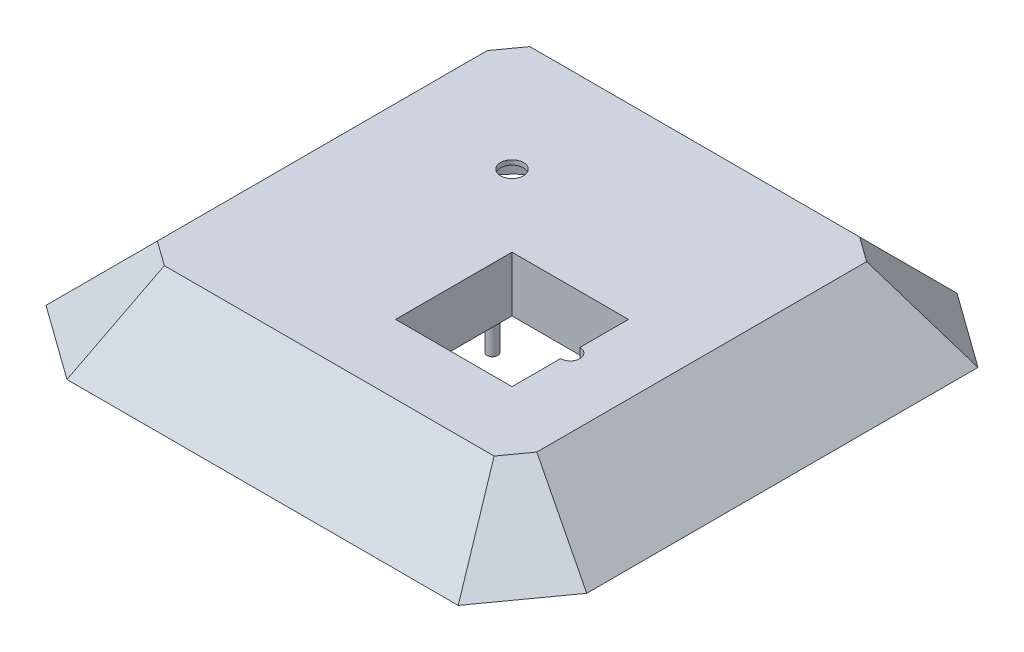
SolidWorks part; units mm, degrees
ref_plane "Front Plane" through (0, 0, 0) normal (0, 0, 1) x (1, 0, 0)
ref_plane "Top Plane" through (0, 0, 0) normal (0, 1, 0) x (1, 0, 0)
ref_plane "Right Plane" through (0, 0, 0) normal (1, 0, 0) x (0, 0, -1)
sketch "Sketch1" plane through (0, 0, 0) normal (0, 1, 0) x (1, 0, 0)
  line L0 (-47.3454, -21.7516) -> (37.6546, -21.7516)
  line L1 (37.6546, -21.7516) -> (49.3368, -5.5181)
  line L2 (49.3368, -5.5181) -> (49.3368, 79.4819)
  line L3 (49.3368, 79.4819) -> (33.1033, 91.1641)
  line L4 (33.1033, 91.1641) -> (-51.8967, 91.1641)
  line L5 (-51.8967, 91.1641) -> (-63.5789, 74.9306)
  line L6 (-63.5789, 74.9306) -> (-63.5789, -10.0694)
  line L7 (-63.5789, -10.0694) -> (-47.3454, -21.7516)
  dimension "D2" = 85
  dimension "D3" = 85
  dimension "D4" = 144.26
  dimension "D5" = 144.26
  dimension "D6" = 85
  dimension "D7" = 144.26
  dimension "D8" = 20
  dimension "D9" = 85
  dimension "D10" = 20
  dimension "D11" = 20
extrude "Boss-Extrude2" add sketch "Sketch1" along normal blind 16
sketch "Sketch4" plane through (0, 0, 0) normal (0, -1, 0) x (1, 0, 0)
  line L16 (-42.1868, 5.7516) -> (-47.5789, 1.8712)
  line L17 (-47.5789, 1.8712) -> (-47.5789, -69.772)
  line L18 (-47.5789, -69.772) -> (-43.6985, -75.1641)
  line L19 (-43.6985, -75.1641) -> (27.9447, -75.1641)
  line L20 (27.9447, -75.1641) -> (33.3368, -71.2838)
  line L21 (33.3368, -71.2838) -> (33.3368, 0.3594)
  line L22 (33.3368, 0.3594) -> (29.4564, 5.7516)
  line L23 (29.4564, 5.7516) -> (-42.1868, 5.7516)
  line L24 (-42.1868, 5.7516) -> (-47.5789, 1.8712)
  line L25 (-47.5789, 1.8712) -> (-47.5789, -69.772)
  line L26 (-47.5789, -69.772) -> (-43.6985, -75.1641)
  line L27 (-43.6985, -75.1641) -> (27.9447, -75.1641)
  line L28 (27.9447, -75.1641) -> (33.3368, -71.2838)
  line L29 (33.3368, -71.2838) -> (33.3368, 0.3594)
  line L30 (33.3368, 0.3594) -> (29.4564, 5.7516)
  line L31 (29.4564, 5.7516) -> (-42.1868, 5.7516)
  dimension "D1" = 16
chamfer "Chamfer1" distance 16 angle 45 8 edges at (-63.5789, 16, -32.4306) (-57.7378, 16, -83.0473) (-9.3967, 16, -91.1641) (41.22, 16, -85.323) (49.3368, 16, -36.9819) (43.4957, 16, 13.6348) (-4.8454, 16, 21.7516) (-55.4621, 16, 15.9105)
extrude "Cut-Extrude3" cut sketch "Sketch4" against normal blind 4
sketch "Sketch6" plane through (0, 16, 0) normal (0, 1, 0) x (1, 0, 0)
  line L0 (33.3368, -0.3594) -> (33.3368, 71.2838) construction
  line L1 (-6.9632, 34.5484) -> (18.3368, 34.5484)
  line L2 (-6.9632, 34.5484) -> (-6.9632, 9.2484)
  line L3 (-6.9632, 9.2484) -> (18.3368, 9.2484)
  line L4 (18.3368, 34.5484) -> (18.3368, 9.2484)
  line L5 (-42.1868, -5.7516) -> (29.4564, -5.7516) construction
  dimension "D1" = 25.3
  dimension "D2" = 25.3
  dimension "D3" = 15
  dimension "D4" = 15
extrude "Cut-Extrude4" cut sketch "Sketch6" against normal up to next
sketch "Sketch7" plane through (0, 4, 0) normal (0, -1, 0) x (1, 0, 0)
  line L0 (18.3368, -9.2484) -> (18.3368, -34.5484) construction
  circle A0 centre (18.3368, -21.8984) radius 2.0981
extrude "Cut-Extrude5" cut sketch "Sketch7" against normal up to next
sketch "Sketch8" plane through (0, 4, 0) normal (0, -1, 0) x (1, 0, 0)
  line L0 (-11.7632, -21.9984) -> (30.1662, -21.9984) construction
  line L1 (-11.7632, -8.8984) -> (24.2368, -8.8984)
  line L2 (-11.7632, -8.8984) -> (-11.7632, -35.0984)
  line L3 (-11.7632, -35.0984) -> (24.2368, -35.0984)
  line L4 (24.2368, -8.8984) -> (24.2368, -35.0984)
  line L5 (6.2368, -8.8984) -> (6.2368, -38.2867) construction
  line L6 (33.3368, -71.2838) -> (33.3368, 0.3594) construction
  line L7 (29.4564, 5.7516) -> (-42.1868, 5.7516) construction
  circle A0 centre (-9.2132, -11.4484) radius 1.15
  circle A1 centre (21.6868, -11.4484) radius 1.15
  circle A2 centre (21.6868, -32.5484) radius 1.15
  circle A3 centre (-9.2132, -32.5484) radius 1.15
  dimension "D3" = 2.3
  dimension "D4" = 2.55
  dimension "D5" = 2.55
  dimension "D6" = 9.1
  dimension "D1" = 36
  dimension "D2" = 26.2
  dimension "D7" = 14.65
extrude "Boss-Extrude3" add sketch "Sketch8" along normal blind 7 contours A0 | A1 | A2 | A3 region at (-9.2132, 4, -11.4484) region at (21.6868, 4, -11.4484) region at (21.6868, 4, -32.5484)
sketch "Sketch9" plane through (0, 4, 0) normal (0, -1, 0) x (1, 0, 0)
  line L2 (-47.5789, 1.8712) -> (-47.5789, -69.772) construction
  line L3 (-43.6985, -75.1641) -> (27.9447, -75.1641) construction
  circle A0 centre (-22.5789, -50.1641) radius 15.65
  dimension "D1" = 25
  dimension "D2" = 25
  dimension "D3" = 31.3
extrude "Cut-Extrude6" cut sketch "Sketch9" against normal blind 11
sketch "Sketch10" plane through (0, 15, 0) normal (0, -1, 0) x (1, 0, 0)
  circle A0 centre (-22.5789, -50.1641) radius 2.5
  dimension "D1" = 5
extrude "Cut-Extrude7" cut sketch "Sketch10" against normal up to next
